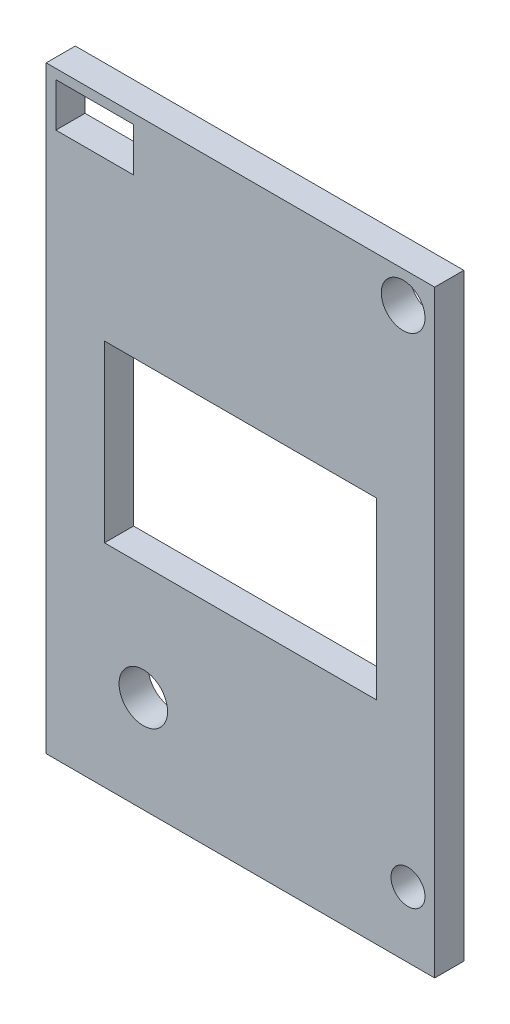
SolidWorks part; units mm, degrees
material "ASTM A36 Steel"
ref_plane "Front Plane" through (0, 0, 0) normal (0, 0, 1) x (1, 0, 0)
ref_plane "Top Plane" through (0, 0, 0) normal (0, 1, 0) x (1, 0, 0)
ref_plane "Right Plane" through (0, 0, 0) normal (1, 0, 0) x (0, 0, -1)
sketch "Sketch1" plane through (0, 0, 0) normal (0, 0, 1) x (1, 0, 0)
  line L0 (9, 60.6) -> (1, 56.1) construction
  line L1 (1, 60.6) -> (9, 60.6)
  line L2 (1, 60.6) -> (1, 56.1)
  line L3 (1, 56.1) -> (9, 56.1)
  line L4 (9, 60.6) -> (9, 56.1)
  line L5 (0, 30.8) -> (40, 30.8) construction
  line L6 (0, 20) -> (20, 20) construction
  line L7 (20, 20) -> (20, 0) construction
  line L8 (0, 61.6) -> (40, 61.6)
  line L9 (0, 61.6) -> (0, 0)
  line L10 (0, 0) -> (40, 0)
  line L11 (40, 61.6) -> (40, 0)
  line L12 (20, 20) -> (0, 0) construction
  line L13 (20, 61.6) -> (20, 0) construction
  line L14 (34, 39.8) -> (6, 39.8)
  line L15 (34, 39.8) -> (34, 21.8)
  line L16 (34, 21.8) -> (6, 21.8)
  line L17 (6, 39.8) -> (6, 21.8)
  circle A0 centre (37.25, 6.75) radius 1.75
  circle A1 centre (36.75, 58.35) radius 2.25
  circle A2 centre (10, 10) radius 2.5
  point P9 (5, 58.35)
  point P12 (36.75, 60.6)
  point P15 (36.75, 56.1)
  point P17 (39, 58.35)
  point P20 (39, 6.75)
  point P21 (37.25, 5)
  point P31 (34, 30.8)
  point P32 (20, 21.8)
  dimension "D1" = 3.5
  dimension "D4" = 4.5
  dimension "D6" = 1
  dimension "D14" = 5
  dimension "D2" = 4.5
  dimension "D3" = 8
  dimension "D5" = 1
  dimension "D7" = 40
  dimension "D8" = 1
  dimension "D9" = 1
  dimension "D10" = 61.6
  dimension "D11" = 1
  dimension "D12" = 5
  dimension "D13" = 20
  dimension "D15" = 28
  dimension "D16" = 18
  dimension "D17" = 30.8
extrude "Boss-Extrude1" add sketch "Sketch1" along normal blind 3
